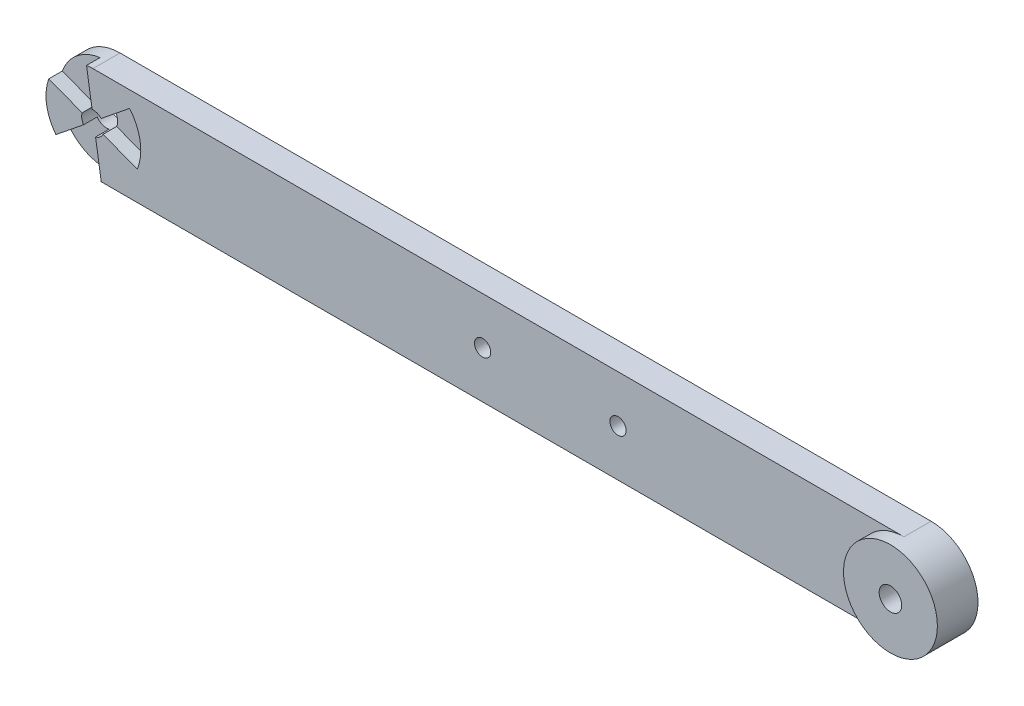
SolidWorks part; units mm, degrees
ref_plane "Front Plane" through (0, 0, 0) normal (0, 0, 1) x (1, 0, 0)
ref_plane "Top Plane" through (0, 0, 0) normal (0, 1, 0) x (1, 0, 0)
ref_plane "Right Plane" through (0, 0, 0) normal (1, 0, 0) x (0, 0, -1)
sketch "Sketch1" plane through (0, 0, 0) normal (0, 0, 1) x (1, 0, 0)
  line L0 (179.7, -10.4) -> (0, -10.4)
  line L1 (179.7, 10.4) -> (0, 10.4)
  circle A4 centre (0, 0) radius 2.5
  circle A5 centre (179.7, 0) radius 2.5
  arc A6 (0, 10.4) -> (0, -10.4) centre (0, 0) ccw
  arc A7 (179.7, -10.4) -> (179.7, 10.4) centre (179.7, 0) ccw
  arc A9 (0, -10.4) -> (0, 10.4) centre (0, 0) ccw construction
  circle A10 centre (0, 0) radius 10.4 construction
  arc A11 (179.7, 10.4) -> (179.7, -10.4) centre (179.7, 0) ccw construction
  circle A12 centre (179.7, 0) radius 10.4 construction
  circle A13 centre (179.7, 0) radius 1.4996 construction
  circle A15 centre (0, 0) radius 2.4001
  point P11 (170.2346, 97.4995)
  point P18 (75.4, 97.5)
  dimension "D1" = 5
  dimension "D3" = 1.0004
  dimension "D4" = 4.8001
  dimension "D2" = 10.4
  dimension "D5" = 179.7
extrude "Boss-Extrude1" add sketch "Sketch1" along normal blind 6 contours L0 A7 L1 A6 A4 A5 region at (89.85, 0, 0)
sketch "Sketch6" plane through (0, 0, 0) normal (0, 0, -1) x (-1, 0, 0)
  line L0 (0, 0) -> (6.6622, 8.2447) construction
  line L1 (0, 0) -> (-10.4, 0) construction
  line L2 (0, 0) -> (9.892, 3.8091) construction
  line L3 (0, 0) -> (1.6472, 10.4712) construction
  line L4 (2.3974, 0.7088) -> (9.9638, 3.6224)
  line L5 (0.1897, 2.4928) -> (1.4497, 10.5023)
  line L6 (-0.5848, -2.4306) -> (-1.8448, -10.4401)
  line L7 (0.0719, -0.1866) -> (9.9638, 3.6224) construction
  line L8 (-0.1976, 0.0311) -> (1.4497, 10.5023) construction
  line L9 (2.064, -1.4107) -> (8.3704, -6.5066)
  line L10 (0.1257, 0.1556) -> (8.3704, -6.5066) [skipped]
  line L11 (-0.1976, 0.0311) -> (-1.8448, -10.4401) [skipped]
  line L12 (0.0719, -0.1866) -> (-9.8201, -3.9957) [skipped]
  line L13 (0.1257, 0.1556) -> (-8.119, 6.8177) [skipped]
  line L14 (-1.8126, 1.7218) -> (-8.119, 6.8177)
  line L15 (-2.2537, -1.0821) -> (-9.8201, -3.9957)
  circle A0 centre (0, 0) radius 10.4 construction
  arc A1 (0, -10.4) -> (0, 10.4) centre (0, 0) ccw construction
  arc A2 (9.9621, 3.6217) -> (1.4494, 10.5004) centre (0, 0) ccw
  arc A3 (9.9621, 3.6217) -> (1.4494, 10.5004) centre (0, 0) ccw
  arc A4 (9.9621, 3.6217) -> (1.4494, 10.5004) centre (0, 0) ccw
  circle A5 centre (0, 0) radius 2.5 construction
  arc A6 (2.3974, 0.7088) -> (0.1897, 2.4928) centre (0, 0) ccw
  arc A7 (-0.5848, -2.4306) -> (2.064, -1.4107) centre (0, 0) ccw
  circle A8 centre (0, 0) radius 10.6 construction
  arc A9 (-1.8445, -10.4383) -> (8.369, -6.5054) centre (0, 0) ccw
  arc A10 (-1.8126, 1.7218) -> (-2.2537, -1.0821) centre (0, 0) ccw
  arc A11 (-8.1176, 6.8165) -> (-9.8183, -3.995) centre (0, 0) ccw
  point P8 (-0.7033, -1.0005)
  point P13 (7.6704, -5.9409)
  point P14 (0.0719, -0.1866)
  point P15 (9.124, 3.299)
  point P22 (10.1368, 3.0991)
  point P27 (0, 0)
  point P34 (0, 0)
  point P51 (0, 0)
  circle M6 centre (0, 0) radius 2.5
  line M8 (-179.7, -10.4) -> (0, -10.4)
  arc M9 (0, -10.4) -> (0, 10.4) centre (0, 0) ccw
  dimension "D3" = 60
  dimension "D2" = 128.94
  dimension "D4" = 30
  dimension "D6" = 0.2
  dimension "D8" = 3
  dimension "D1" = 0.2
  dimension "D5" = 0.2
  dimension "D7" = 3
extrude "Cut-Extrude3" cut sketch "Sketch6" against normal blind 3 contours L5 L4 M6 M9 | L9 L6 M6 M8 M9 | L14 A11 L15 M6 region at (-4.3061, 5.329, 0) region at (-2.4553, -6.4005, 0) region at (6.8883, 1.0836, 0)
sketch "Sketch4" plane through (0, 0, 0) normal (0, 0, -1) x (-1, 0, 0)
  arc A0 (-179.7, 10.4) -> (-179.7, -10.4) centre (-179.7, 0) ccw construction
  arc A1 (-179.7, 10.4) -> (-179.7, -10.4) centre (-179.7, 0) ccw
  arc A2 (-179.7, 10.4) -> (-179.7, -10.4) centre (-179.7, 0) cw
  circle A3 centre (-179.7, 0) radius 2.5 construction
  circle A4 centre (-179.7, 0) radius 2.5
extrude "Boss-Extrude2" add sketch "Sketch4" along normal blind 3
hole_wizard "M3 Clearance Hole2" positions "Sketch9" profile "Sketch8" hole size "M3" standard "ANSI Metric" end condition through all
sketch "Sketch9" plane through (0, 0, 6) normal (0, 0, 1) x (1, 0, 0)
  line L0 (0, 0) -> (86.34, 0) construction
  line L1 (86.34, 0) -> (116.34, 0) construction
  point P2 (86.34, 0)
  point P8 (86.34, 0)
  point P9 (116.34, 0)
  point P19 (116.34, 0)
  point P22 (86.34, 0)
  dimension "D1" = 30
  dimension "D2" = 86.34
sketch "Sketch8" plane through (86.34, 0, 6) normal (1, 0, 0) x (0, -1, 0)
  line L0 (0, 0) -> (0, 9)
  line L1 (0, 9) -> (1.8, 9)
  line L2 (1.8, 9) -> (1.8, 0)
  line L5 (1.8, 0) -> (0, 0)
  line L11 (0, -6.35) -> (0, 107.95) construction
  dimension "Thru Hole Dia." = 3.6
  dimension "Thru Hole Depth" = 9
mirror "Mirror1" about plane through (0, 0, 0) normal (0, 0, 1) of bodies 108 103
delete or keep bodies "Body-Delete/Keep 1" type delete bodies bodies 108
